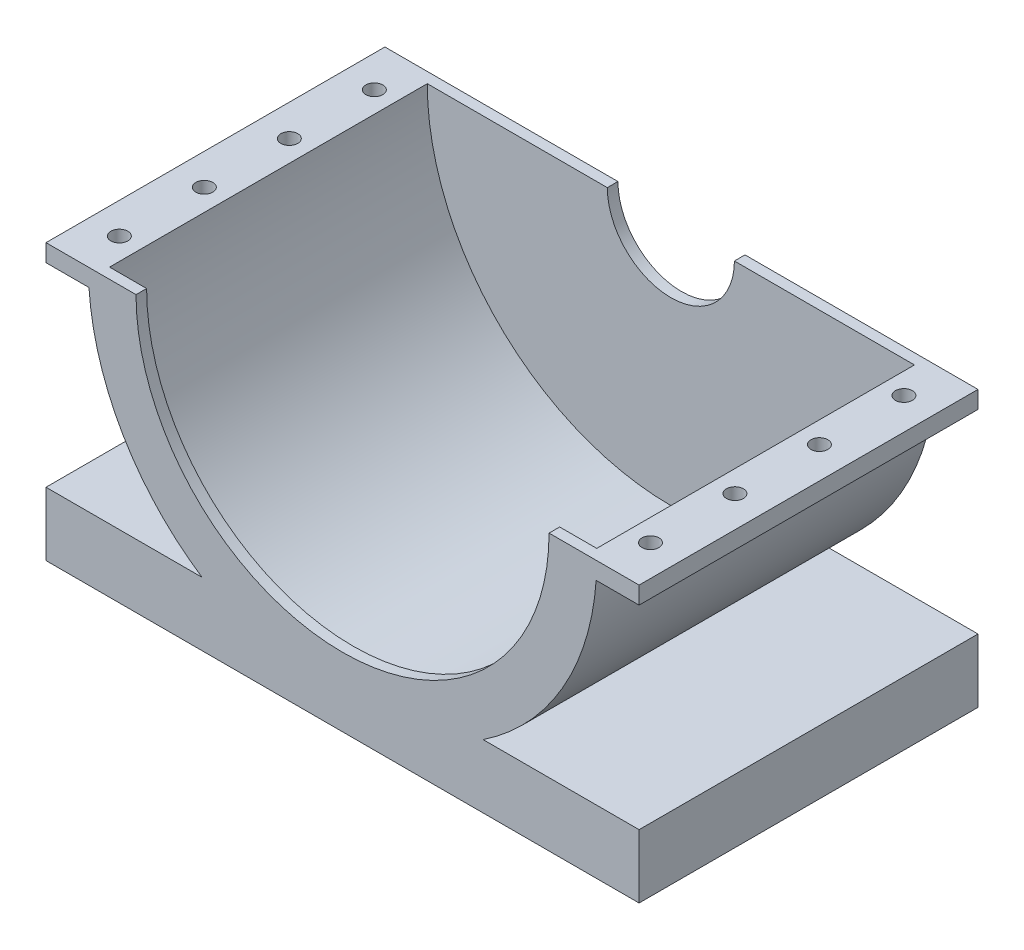
SolidWorks part; units mm, degrees
ref_plane "Front Plane" through (0, 0, 0) normal (0, 0, 1) x (1, 0, 0)
ref_plane "Top Plane" through (0, 0, 0) normal (0, 1, 0) x (1, 0, 0)
ref_plane "Right Plane" through (0, 0, 0) normal (1, 0, 0) x (0, 0, -1)
sketch "Sketch1" plane through (0, 0, 0) normal (0, 0, 1) x (1, 0, 0)
  line L0 (-175, 0) -> (-143.75, 0)
  line L1 (-175, 0) -> (-175, -10.25)
  line L2 (-175, -10.25) -> (-149.6494, -10.25)
  line L3 (149.6494, -10.25) -> (175, -10.25)
  line L4 (175, -10.25) -> (175, 0)
  line L5 (143.75, 0) -> (175, 0)
  line L6 (-175, -125) -> (-82.9156, -125)
  line L7 (-175, -125) -> (-175, -162.5)
  line L8 (-175, -162.5) -> (175, -162.5)
  line L9 (175, -125) -> (175, -162.5)
  line L10 (-30.454, -140.4871) -> (175, -162.5) construction
  line L11 (-175, -162.5) -> (175, -125) construction
  line L12 (82.9156, -125) -> (175, -125)
  arc A0 (-143.75, 0) -> (143.75, 0) centre (0, 0) ccw
  arc A1 (-149.6494, -10.25) -> (-82.9156, -125) centre (0, 0) ccw
  arc A2 (82.9156, -125) -> (149.6494, -10.25) centre (0, 0) ccw
  point P10 (0, -143.75)
  dimension "D1" = 300
  dimension "D2" = 287.5
  dimension "D3" = 350
  dimension "D4" = 10.25
  dimension "D5" = 37.5
  dimension "D6" = 125
  dimension "D7" = 350
extrude "Boss-Extrude1" add sketch "Sketch1" along normal blind 100 and the other way blind 100
sketch "Sketch2" plane through (0, 0, 100) normal (0, 0, 1) x (1, 0, 0)
  line L0 (-143.75, 0) -> (-121.875, 0)
  line L1 (121.875, 0) -> (143.75, 0)
  arc A1 (-121.875, 0) -> (121.875, 0) centre (0, 0) ccw
  arc A2 (-143.75, 0) -> (143.75, 0) centre (0, 0) ccw
  dimension "D1" = 243.75
extrude "Boss-Extrude2" add sketch "Sketch2" against normal blind 6.25
sketch "Sketch3" plane through (0, 0, -100) normal (0, 0, -1) x (-1, 0, 0)
  line L0 (-143.75, 0) -> (-37.5, 0)
  line L1 (37.5, 0) -> (143.75, 0)
  arc A0 (-143.75, 0) -> (143.75, 0) centre (0, 0) ccw
  arc A1 (-37.5, 0) -> (37.5, 0) centre (0, 0) ccw
  dimension "D1" = 75
extrude "Boss-Extrude3" add sketch "Sketch3" against normal blind 6.25
sketch "Sketch4" plane through (0, 0, 0) normal (0, 1, 0) x (1, 0, 0)
  line L0 (175, 100) -> (37.5, 100) construction
  line L1 (175, 100) -> (175, -100) construction
  circle A0 centre (156.25, 75) radius 5
  circle A1 centre (156.404, 25.0002) radius 5
  circle A2 centre (156.5579, -24.9995) radius 5
  circle A3 centre (156.7119, -74.9993) radius 5
  circle A4 centre (-156.7119, -74.9993) radius 5
  circle A5 centre (-156.5579, -24.9995) radius 5
  circle A6 centre (-156.404, 25.0002) radius 5
  circle A7 centre (-156.25, 75) radius 5
  point P6 (0, 0)
  point P7 (0, 0)
  dimension "D1" = 10
  dimension "D2" = 25
  dimension "D3" = 18.75
  dimension "D5" = 49.9998
  dimension "D6" = 313.4238
  dimension "D4" = 4
extrude "Cut-Extrude2" cut sketch "Sketch4" against normal up to next
